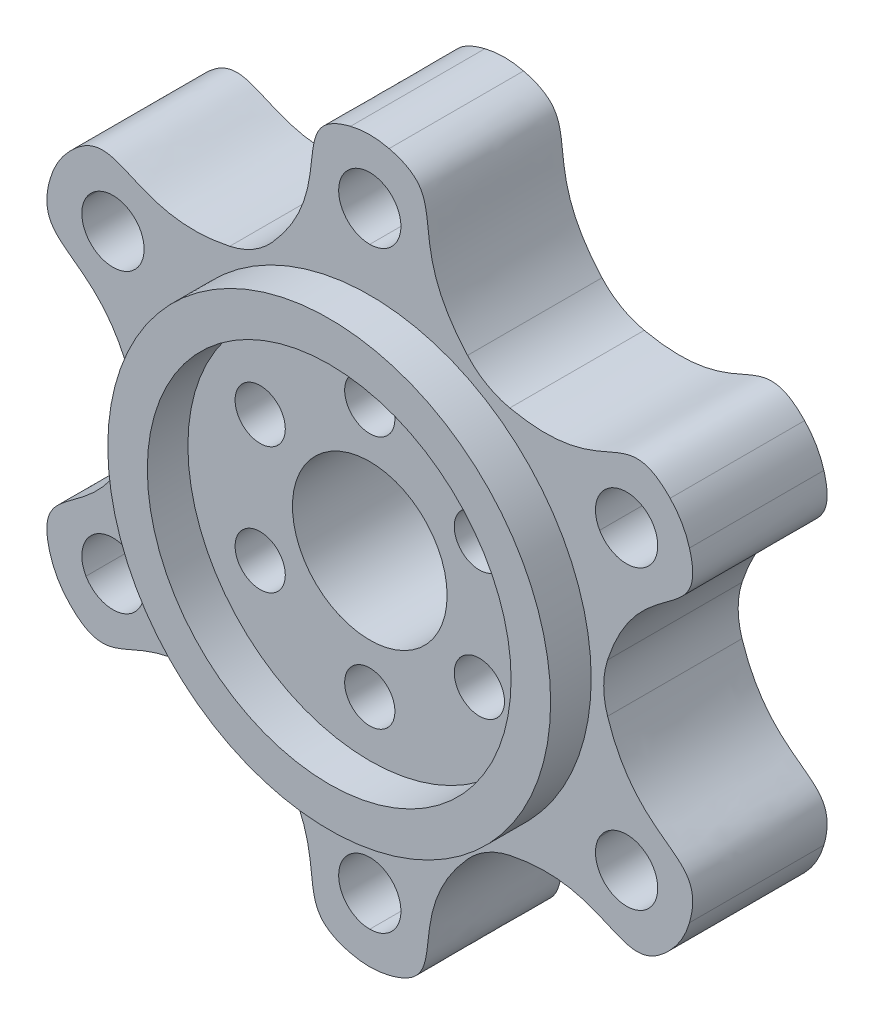
SolidWorks part; units mm, degrees
ref_plane "Front Plane" through (0, 0, 0) normal (0, 0, 1) x (1, 0, 0)
ref_plane "Top Plane" through (0, 0, 0) normal (0, 1, 0) x (1, 0, 0)
ref_plane "Right Plane" through (0, 0, 0) normal (1, 0, 0) x (0, 0, -1)
sketch "Sketch1" plane through (0, 0, 0) normal (0, 0, 1) x (1, 0, 0)
  line L0 (0, -55) -> (0, 55) construction
  line L1 (0, 0) -> (0, 45.72) construction
  circle A0 centre (0, 0) radius 9.779
  circle A1 centre (0, 0) radius 45.72
  circle A2 centre (0, 16.002) radius 3.175
  circle A3 centre (13.8581, 8.001) radius 3.175
  circle A4 centre (13.8581, -8.001) radius 3.175
  circle A5 centre (0, -16.002) radius 3.175
  circle A6 centre (-13.8581, -8.001) radius 3.175
  circle A7 centre (-13.8581, 8.001) radius 3.175
  circle A8 centre (0, 37.5) radius 3.937
  circle A10 centre (32.476, 18.75) radius 3.937
  circle A11 centre (32.476, -18.75) radius 3.937
  circle A12 centre (0, -37.5) radius 3.937
  circle A13 centre (-32.476, -18.75) radius 3.937
  circle A14 centre (-32.476, 18.75) radius 3.937
  point P21 (0, 0)
  point P36 (0, 0)
  dimension "D1" = 19.558
  dimension "D2" = 91.44
  dimension "D3" = 6.35
  dimension "D6" = 7.874
  dimension "D4" = 16.002
  dimension "D8" = 37.5
  dimension "D5" = 6
  dimension "D7" = 6
extrude "Boss-Extrude3" add sketch "Sketch1" along normal blind 17
sketch "Sketch2" plane through (0, 0, 17) normal (0, 0, 1) x (1, 0, 0)
  line L0 (0, -9.35) -> (0, 9.35) construction
  line L1 (-32.476, 18.75) -> (0, 37.5) construction
  line L2 (-16.238, 28.125) -> (-4.8895, 8.4689) construction
  line L3 (16.1981, 28.148) -> (4.8496, 8.4918) construction
  line L6 (32.476, -18.75) -> (32.476, 18.75) construction
  line L7 (32.476, 18.75) -> (0, 37.5) construction
  line L8 (9.35, 0) -> (-9.35, 0) construction
  circle A0 centre (0, 0) radius 27.94 construction
  circle A1 centre (0, 0) radius 45.72 construction
  circle A2 centre (0, 0) radius 9.779 construction
  circle A3 centre (0, 0) radius 45.72
  spline S0 degree 3 poles (-14.625, 25.3312) (-1.5745, 37.1177) (-13.1193, 43.9586) (0, 45.72) knots 0 0 0 0 1 1 1 1
  spline S1 degree 3 poles (14.625, 25.3312) (1.5745, 37.1177) (13.1193, 43.9586) (0, 45.72) knots 0 0 0 0 1 1 1 1
  spline S2 degree 3 poles (-29.25, 0) (-32.9321, 17.1953) (-44.6289, 10.6177) (-39.5947, 22.86) knots 0 0 0 0 1 1 1 1
  spline S3 degree 3 poles (-14.625, 25.3312) (-31.3576, 19.9224) (-31.5096, 33.3409) (-39.5947, 22.86) knots 0 0 0 0 1 1 1 1
  spline S4 degree 3 poles (-14.625, -25.3312) (-31.3576, -19.9224) (-31.5096, -33.3409) (-39.5947, -22.86) knots 0 0 0 0 1 1 1 1
  spline S5 degree 3 poles (-29.25, 0) (-32.9321, -17.1953) (-44.6289, -10.6177) (-39.5947, -22.86) knots 0 0 0 0 1 1 1 1
  spline S6 degree 3 poles (14.625, -25.3312) (31.3576, -19.9224) (31.5096, -33.3409) (39.5947, -22.86) knots 0 0 0 0 1 1 1 1
  spline S7 degree 3 poles (29.25, 0) (32.9321, -17.1953) (44.6289, -10.6177) (39.5947, -22.86) knots 0 0 0 0 1 1 1 1
  spline S8 degree 3 poles (14.625, -25.3312) (1.5745, -37.1177) (13.1193, -43.9586) (0, -45.72) knots 0 0 0 0 1 1 1 1
  spline S9 degree 3 poles (-14.625, -25.3312) (-1.5745, -37.1177) (-13.1193, -43.9586) (0, -45.72) knots 0 0 0 0 1 1 1 1
  spline S10 degree 3 poles (29.25, 0) (32.9321, 17.1953) (44.6289, 10.6177) (39.5947, 22.86) knots 0 0 0 0 1 1 1 1
  spline S11 degree 3 poles (14.625, 25.3312) (31.3576, 19.9224) (31.5096, 33.3409) (39.5947, 22.86) knots 0 0 0 0 1 1 1 1
  point P2 (0, 0)
  point P5 (-16.238, 28.125)
  point P6 (16.1981, 28.148)
  point P35 (-13.97, 24.1967)
  point P38 (-13.97, 24.1967)
  point P39 (14.8098, 25.7434)
  point P40 (14.6344, 25.4395)
  point P41 (-39.5947, 22.86)
  circle M8 centre (0, 0) radius 45.72
  dimension "D1" = 55.88
  dimension "D2" = 18.796
  dimension "D3" = 29.25
extrude "Cut-Extrude1" cut sketch "Sketch2" against normal blind 22.86 contours S1 S11 M8 | S5 S2 A3 | S10 S7 A3 | S6 S8 A3 | S9 S4 M8 | S3 S0 M8 region at (38.672, 0, 17) region at (19.336, 33.4909, 17) region at (19.336, -33.4909, 17) region at (-19.336, 33.4909, 17) region at (-19.336, -33.4909, 17) region at (-38.672, 0, 17)
sketch "Sketch4" plane through (0, 0, 17) normal (0, 0, 1) x (1, 0, 0)
  circle A0 centre (0, 0) radius 9.779 construction
  circle A1 centre (0, 0) radius 9.779 construction
  circle A2 centre (0, 0) radius 28
  circle A3 centre (0, 0) radius 23
  dimension "D1" = 56
  dimension "D2" = 46
extrude "Boss-Extrude4" add sketch "Sketch4" along normal blind 5.1308 contours A2 | A3
ref_plane "Plane1" through (0, 0, 0) normal (1, 0, 0) x (0, 0, -1)
ref_plane "Plane2" through (0, 0, 0) normal (-0.5, -0.866, 0) x (-0.866, 0.5, 0)
ref_plane "Plane3" through (0, 0, 0) normal (-0.5, 0.866, 0) x (0.866, 0.5, 0)
split line "Split Line1"
split line "Split Line2"
split line "Split Line3"
ref_axis "Axis1" through (0, 0, 17) along (0, 0, -1)
fillet "Fillet1" radius 10 12 edges at (29.25, 0, 8.5) (39.5947, -22.86, 8.5) (0, -45.72, 8.5) (14.625, -25.3312, 8.5) (-14.625, -25.3312, 8.5) (-39.5947, -22.86, 8.5) (-29.25, 0, 8.5) (-39.5947, 22.86, 8.5) (-14.625, 25.3312, 8.5) (14.625, 25.3312, 8.5) (39.5947, 22.86, 8.5) (0, 45.72, 8.5)
